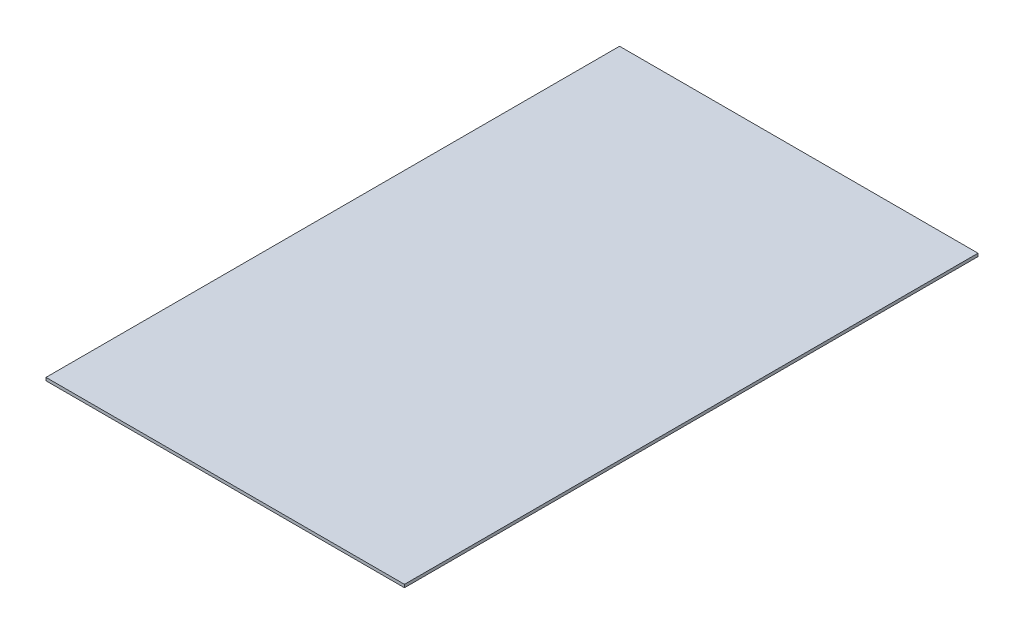
SolidWorks part; units mm, degrees
ref_plane "Front Plane" through (0, 0, 0) normal (0, 0, 1) x (1, 0, 0)
ref_plane "Top Plane" through (0, 0, 0) normal (0, 1, 0) x (1, 0, 0)
ref_plane "Right Plane" through (0, 0, 0) normal (1, 0, 0) x (0, 0, -1)
sketch "Sketch1" plane through (0, 0, 0) normal (0, 1, 0) x (1, 0, 0)
  line L1 (-190.5, -304.8) -> (190.5, -304.8)
  line L2 (-190.5, -304.8) -> (-190.5, 304.8)
  line L3 (-190.5, 304.8) -> (190.5, 304.8)
  line L4 (190.5, -304.8) -> (190.5, 304.8)
  line L5 (0, 304.8) -> (0, -304.8) construction
  line L6 (-190.5, 0) -> (190.5, 0) construction
  point P0 (0, 0)
  dimension "D1" = 381
  dimension "D2" = 609.6
extrude "Boss-Extrude1" add sketch "Sketch1" along normal blind 3.175
